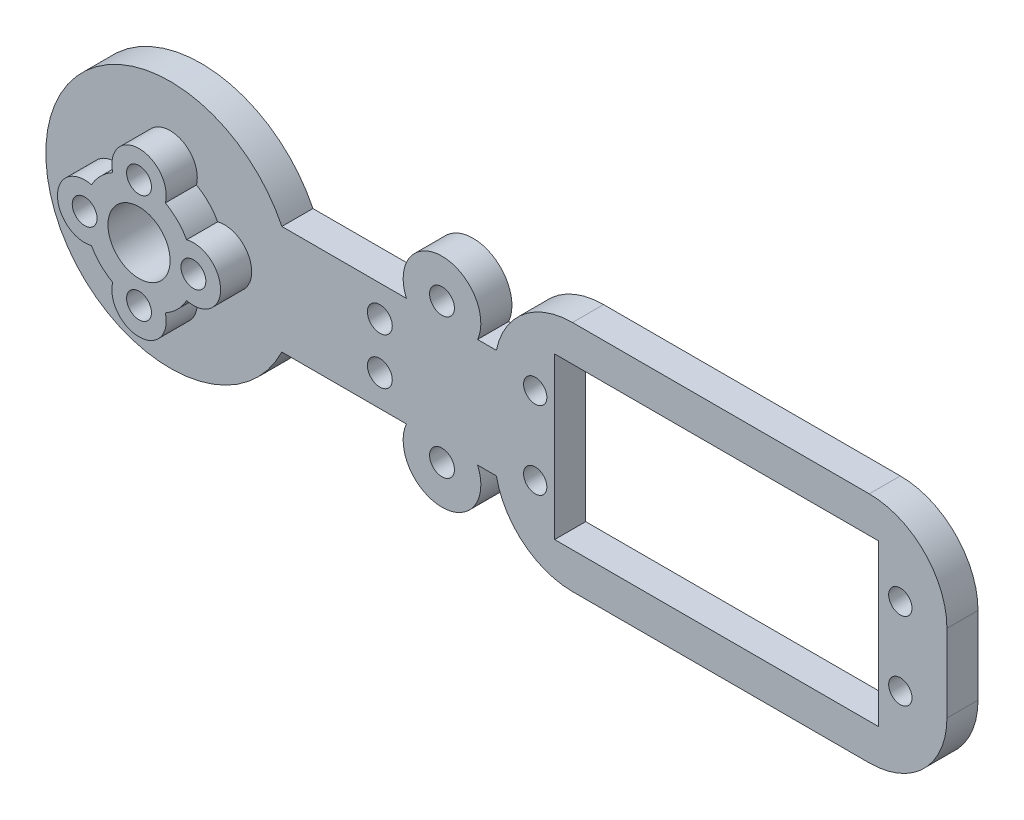
SolidWorks part; units mm, degrees
ref_plane "Front Plane" through (0, 0, 0) normal (0, 0, 1) x (1, 0, 0)
ref_plane "Top Plane" through (0, 0, 0) normal (0, 1, 0) x (1, 0, 0)
ref_plane "Right Plane" through (0, 0, 0) normal (1, 0, 0) x (0, 0, -1)
sketch "Main_web_profile" plane through (0, 0, 0) normal (0, 0, 1) x (1, 0, 0)
  line L1 (0, -7) -> (60, -7)
  line L2 (0, -7) -> (0, 7)
  line L3 (0, 7) -> (60, 7)
  line L4 (60, -7) -> (60, 7)
  dimension "D1" = 60
  dimension "D2" = 14
  dimension "D3" = 7
extrude "Main_web" add sketch "Main_web_profile" along normal blind 4
sketch "Shoulder_horn_flange_profile" plane through (0, 0, 0) normal (0, 0, 1) x (1, 0, 0)
  circle A0 centre (0, 0) radius 16
  dimension "D1" = 32
extrude "Shoulder_horn_flange" add sketch "Shoulder_horn_flange_profile" along normal blind 4
sketch "Elbow_servo_mount_profile" plane through (0, 0, 0) normal (0, 0, 1) x (1, 0, 0)
  line L1 (42, -14) -> (90, -14)
  line L2 (42, -14) -> (42, 14)
  line L3 (42, 14) -> (90, 14)
  line L4 (90, -14) -> (90, 14)
  dimension "D1" = 48
  dimension "D2" = 28
  dimension "D3" = 42
  dimension "D4" = 14
extrude "Elbow_servo_mount" add sketch "Elbow_servo_mount_profile" along normal blind 4
sketch "SG90_body_clearance_profile" plane through (0, 0, 0) normal (0, 0, 1) x (1, 0, 0)
  line L1 (53.6, -6.5) -> (77.4, -6.5)
  line L2 (53.6, -6.5) -> (53.6, 6.5)
  line L3 (53.6, 6.5) -> (77.4, 6.5)
  line L4 (77.4, -6.5) -> (77.4, 6.5)
  dimension "D1" = 23.8
  dimension "D2" = 13
  dimension "D3" = 53.6
  dimension "D4" = 6.5
extrude "SG90_body_clearance" cut sketch "SG90_body_clearance_profile" along normal through all from offset 5 offset against normal yes
sketch "Elbow_tab_fasteners_profile" plane through (0, 0, 0) normal (0, 0, 1) x (1, 0, 0)
  circle A0 centre (51, 0) radius 1.3
  circle A1 centre (80, 0) radius 1.3
  dimension "D1" = 2.6
  dimension "D2" = 2.6
  dimension "D3" = 51
  dimension "D4" = 80
extrude "Elbow_tab_fasteners" cut sketch "Elbow_tab_fasteners_profile" along normal through all from offset 50 offset against normal yes
sketch "Shoulder_center_screw_access_profile" plane through (0, 0, 0) normal (0, 0, 1) x (1, 0, 0)
  circle A0 centre (0, 0) radius 4
  dimension "D1" = 8
extrude "Shoulder_center_screw_access" cut sketch "Shoulder_center_screw_access_profile" along normal through all from offset 50 offset against normal yes
sketch "Cable_tie_holes_profile" plane through (0, 0, 0) normal (0, 0, 1) x (1, 0, 0)
  circle A0 centre (27, -3) radius 1.6
  circle A1 centre (27, 3) radius 1.6
  dimension "D1" = 3.2
  dimension "D2" = 3.2
  dimension "D3" = 27
  dimension "D4" = 3
  dimension "D5" = 3
extrude "Cable_tie_holes" cut sketch "Cable_tie_holes_profile" along normal through all from offset 50 offset against normal yes
sketch "Passive_lower_mount_boss_profile" plane through (0, 0, 0) normal (0, 0, 1) x (1, 0, 0)
  circle A0 centre (35, -9) radius 5
  dimension "D1" = 10
  dimension "D2" = 35
  dimension "D3" = 9
extrude "Passive_lower_mount_boss" add sketch "Passive_lower_mount_boss_profile" along normal blind 4
sketch "Passive_upper_mount_boss_profile" plane through (0, 0, 0) normal (0, 0, 1) x (1, 0, 0)
  circle A0 centre (35, 9) radius 5
  dimension "D1" = 10
  dimension "D2" = 35
  dimension "D3" = 9
extrude "Passive_upper_mount_boss" add sketch "Passive_upper_mount_boss_profile" along normal blind 4
sketch "Passive_cheek_standoffs_profile" plane through (0, 0, 0) normal (0, 0, 1) x (1, 0, 0)
  circle A0 centre (35, -9) radius 1.6
  circle A1 centre (35, 9) radius 1.6
  dimension "D1" = 3.2
  dimension "D2" = 3.2
  dimension "D3" = 35
  dimension "D4" = 9
  dimension "D5" = 9
extrude "Passive_cheek_standoffs" cut sketch "Passive_cheek_standoffs_profile" along normal through all from offset 50 offset against normal yes
sketch "Shoulder_dowel_support_hub_profile" plane through (0, 0, 0) normal (0, 0, 1) x (1, 0, 0)
  circle A0 centre (0, 0) radius 7
  circle A1 centre (0, 0) radius 4
  dimension "D1" = 14
  dimension "D2" = 8
extrude "Shoulder_dowel_support_hub" add sketch "Shoulder_dowel_support_hub_profile" along normal blind 4 from offset 4
sketch "Raised_M3_washer_seats_PCD14_profile" plane through (0, 0, 0) normal (0, 0, 1) x (1, 0, 0)
  circle A0 centre (7, 0) radius 3.5
  circle A1 centre (-7, 0) radius 3.5
  circle A2 centre (0, 7) radius 3.5
  circle A3 centre (0, -7) radius 3.5
  dimension "D1" = 7
  dimension "D2" = 7
  dimension "D3" = 7
  dimension "D4" = 7
  dimension "D5" = 7
  dimension "D6" = 7
  dimension "D7" = 7
  dimension "D8" = 7
extrude "Raised_M3_washer_seats_height8" add sketch "Raised_M3_washer_seats_PCD14_profile" along normal blind 4 from offset 4
sketch "Metal_horn_M3_clearance_PCD14_profile" plane through (0, 0, 0) normal (0, 0, 1) x (1, 0, 0)
  circle A0 centre (7, 0) radius 1.6
  circle A1 centre (-7, 0) radius 1.6
  circle A2 centre (0, 7) radius 1.6
  circle A3 centre (0, -7) radius 1.6
  dimension "D1" = 3.2
  dimension "D2" = 3.2
  dimension "D3" = 3.2
  dimension "D4" = 3.2
  dimension "D5" = 7
  dimension "D6" = 7
  dimension "D7" = 7
  dimension "D8" = 7
extrude "Metal_horn_M3_clearance_PCD14" cut sketch "Metal_horn_M3_clearance_PCD14_profile" along normal through all from offset 50 offset against normal yes
sketch "Restore_shoulder_sleeve_bore_profile" plane through (0, 0, 0) normal (0, 0, 1) x (1, 0, 0)
  circle A0 centre (0, 0) radius 4
  dimension "D1" = 8
extrude "Restore_shoulder_sleeve_bore" cut sketch "Restore_shoulder_sleeve_bore_profile" along normal through all from offset 50 offset against normal yes
fillet "Fillet1" radius 7.5 4 edges at (42, -14, 2) (90, -14, 2) (90, 14, 2) (42, 14, 2)
sketch "Larger_elbow_servo_mount_replaces_SG90_opening_profile" plane through (0, 0, 0) normal (0, 0, 1) x (1, 0, 0)
  line L1 (42, -15) -> (100, -15)
  line L2 (42, -15) -> (42, 15)
  line L3 (42, 15) -> (100, 15)
  line L4 (100, -15) -> (100, 15)
  dimension "D1" = 58
  dimension "D2" = 30
  dimension "D3" = 42
  dimension "D4" = 15
extrude "Larger_elbow_servo_mount_replaces_SG90_opening" add sketch "Larger_elbow_servo_mount_replaces_SG90_opening_profile" along normal blind 4
sketch "MG996R_elbow_body_clearance_profile" plane through (0, 0, 0) normal (0, 0, 1) x (1, 0, 0)
  line L1 (49.5, -10.35) -> (91.2, -10.35)
  line L2 (49.5, -10.35) -> (49.5, 10.35)
  line L3 (49.5, 10.35) -> (91.2, 10.35)
  line L4 (91.2, -10.35) -> (91.2, 10.35)
  dimension "D1" = 41.7
  dimension "D2" = 20.7
  dimension "D3" = 49.5
  dimension "D4" = 10.35
extrude "MG996R_elbow_body_clearance" cut sketch "MG996R_elbow_body_clearance_profile" along normal through all from offset 5 offset against normal yes
sketch "MG996R_elbow_tab_fasteners_profile" plane through (0, 0, 0) normal (0, 0, 1) x (1, 0, 0)
  circle A0 centre (47, -5) radius 1.5
  circle A1 centre (47, 5) radius 1.5
  circle A2 centre (94, -5) radius 1.5
  circle A3 centre (94, 5) radius 1.5
  dimension "D1" = 3
  dimension "D2" = 3
  dimension "D3" = 3
  dimension "D4" = 3
  dimension "D5" = 47
  dimension "D6" = 94
  dimension "D7" = 5
  dimension "D8" = 5
extrude "MG996R_elbow_tab_fasteners" cut sketch "MG996R_elbow_tab_fasteners_profile" along normal through all from offset 50 offset against normal yes
fillet "Fillet2" radius 10 4 edges at (42, 15, 2) (42, -15, 2) (100, -15, 2) (100, 15, 2)
